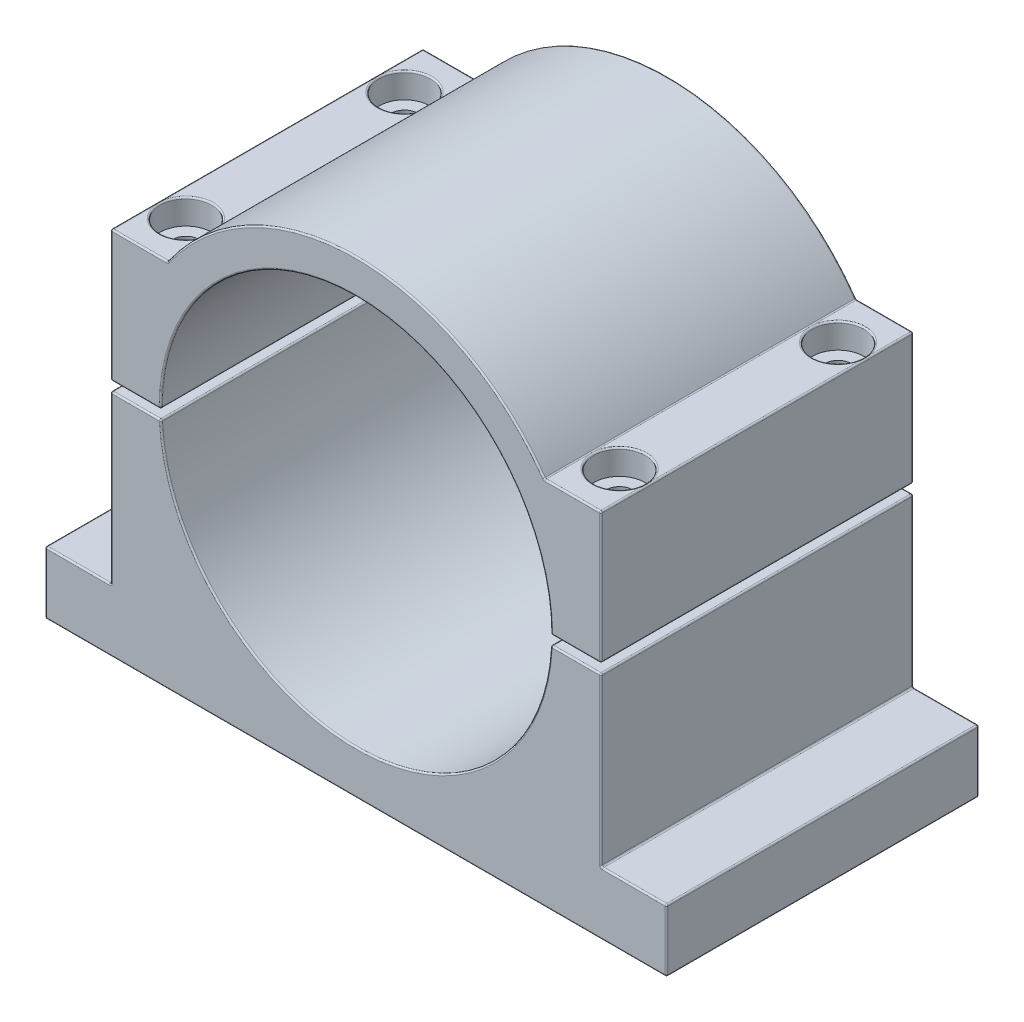
SolidWorks part; units mm, degrees
ref_plane "Спереди" through (0, 0, 0) normal (0, 0, 1) x (1, 0, 0)
ref_plane "Сверху" through (0, 0, 0) normal (0, 1, 0) x (1, 0, 0)
ref_plane "Справа" through (0, 0, 0) normal (1, 0, 0) x (0, 0, -1)
sketch "Эскиз1" plane through (0, 0, 0) normal (0, 0, 1) x (1, 0, 0)
  line L0 (0, 0) -> (0, -76.5) construction
  line L1 (99.5, -76.5) -> (-99.5, -76.5)
  line L2 (-99.5, -76.5) -> (-99.5, -56.5)
  line L3 (-99.5, -56.5) -> (-78.5, -56.5)
  line L4 (-78.5, -56.5) -> (-78.5, 42)
  line L5 (-78.5, 42) -> (-60.3179, 42)
  line L6 (0, 73.5) -> (0, 62.5) construction
  line L7 (0, -76.5) -> (0, -62.5) construction
  line L8 (-78.5, -1.5) -> (0, -1.5) construction
  line L9 (0, 0) -> (78.5, 0)
  line L10 (78.5, -3) -> (-78.5, -3)
  line L11 (0, -3) -> (0, 0)
  line L12 (0, 0) -> (-78.5, 0)
  line L13 (-78.5, -3) -> (-78.5, 0)
  line L14 (78.5, 42) -> (60.3179, 42)
  line L15 (78.5, -56.5) -> (78.5, 42)
  line L16 (99.5, -56.5) -> (78.5, -56.5)
  line L17 (99.5, -76.5) -> (99.5, -56.5)
  circle A0 centre (0, 0) radius 62.5
  circle A1 centre (0, 0) radius 73.5
  point P20 (-62.5, 0)
  dimension "D1" = 125
  dimension "D2" = 150
  dimension "D3" = 199
  dimension "D4" = 20
  dimension "D5" = 21
  dimension "D6" = 14
  dimension "D7" = 98.5
  dimension "D8" = 3
  dimension "D9" = 43.5
extrude "Бобышка-Вытянуть1" add sketch "Эскиз1" along normal mid plane 100 contours A1 L10 L4 L3 L2 L1 L17 L16 L15 | L10 A1 A0 | L9 A1 L12 A0 | A1 L5 L4 L12 | A1 L9 L15 L14 region at (0, -74.3786, 0) region at (0, -71.8708, 0) region at (73.0762, 25.8984, 0) region at (-73.0762, 25.8984, 0) region at (68, 1.6435, 0)
sketch "Эскиз2" plane through (0, 42, 0) normal (0, 1, 0) x (1, 0, 0)
  line L0 (-78.5, 50) -> (-60.3179, 50) construction
  line L1 (-69.409, 50) -> (-69.409, -50) construction
  line L2 (-78.5, -50) -> (-60.3179, -50) construction
  line L4 (69.409, -35) -> (-69.409, -35) construction
  line L5 (69.409, -35) -> (69.409, 35) construction
  line L6 (69.409, 35) -> (-69.409, 35) construction
  line L7 (-69.409, -35) -> (-69.409, 35) construction
  line L8 (69.409, -35) -> (-69.409, 35) construction
  line L9 (69.409, 35) -> (-69.409, -35) construction
  circle A0 centre (-69.409, 35) radius 8.25
  circle A1 centre (-69.409, -35) radius 8.25
  circle A2 centre (69.409, -35) radius 8.25
  circle A3 centre (69.409, 35) radius 8.25
  point P6 (0, 0)
  dimension "D2" = 16.5
  dimension "D3" = 16.5
  dimension "D4" = 16.5
  dimension "D5" = 16.5
  dimension "D1" = 70
extrude "Вырез-Вытянуть1" cut sketch "Эскиз2" against normal blind 8
sketch "Эскиз3" plane through (0, 34, 0) normal (0, 1, 0) x (1, 0, 0)
  circle A0 centre (-69.409, 35) radius 4.25
  circle A1 centre (69.409, 35) radius 4.25
  circle A2 centre (69.409, -35) radius 4.25
  circle A3 centre (-69.409, -35) radius 4.25
  dimension "D1" = 8.5
extrude "Вырез-Вытянуть2" cut sketch "Эскиз3" against normal through all
sketch "Эскиз4" plane through (0, -3, 0) normal (0, 1, 0) x (1, 0, 0)
  circle A0 centre (-69.409, 35) radius 3.1
  circle A1 centre (-69.409, -35) radius 3.1
  circle A2 centre (69.409, -35) radius 3.1
  circle A3 centre (69.409, 35) radius 3.1
  dimension "D1" = 6.2
extrude "Вырез-Вытянуть3" cut sketch "Эскиз4" against normal blind 30
fillet "Скругление1" radius 0.5 28 edges at (-62.5, 0, 0) (62.5, 0, 0) (78.5, 0, 0) (78.5, 42, 0) (61.159, 42, -35) (61.159, 42, 35) (-77.659, 42, -35) (-77.659, 42, 35) (78.5, 21, -50) (69.409, 42, -50) (-69.409, 42, -50) (-70.5, 0, -50) (0, 62.5, -50) (70.5, 0, -50) (-78.5, 42, 0) (-78.5, 0, 0) (-78.5, 21, -50) (60.3179, 42, 0) (-60.3179, 42, 0) (0, 73.5, -50) (0, 62.5, 50) (-70.5, 0, 50) (-78.5, 21, 50) (-69.409, 42, 50) (0, 73.5, 50) (69.409, 42, 50) (78.5, 21, 50) (70.5, 0, 50)
fillet "Скругление2" radius 0.5 30 edges at (99.5, -56.5, 0) (78.5, -56.5, 0) (78.5, -3, 0) (-99.5, -56.5, 0) (-78.5, -3, 0) (-78.5, -56.5, 0) (-99.5, -76.5, 0) (99.5, -76.5, 0) (78.5, -29.75, 50) (89, -56.5, 50) (99.5, -66.5, 50) (0, -76.5, 50) (-99.5, -66.5, 50) (-89, -56.5, 50) (-78.5, -29.75, 50) (-70.464, -3, 50) (70.464, -3, 50) (-70.464, -3, -50) (-78.5, -29.75, -50) (-89, -56.5, -50) (-99.5, -66.5, -50) (0, -76.5, -50) (99.5, -66.5, -50) (89, -56.5, -50) (78.5, -29.75, -50) (70.464, -3, -50) (62.428, -3, 0) (0, -62.5, 50) (-62.428, -3, 0) (0, -62.5, -50)
